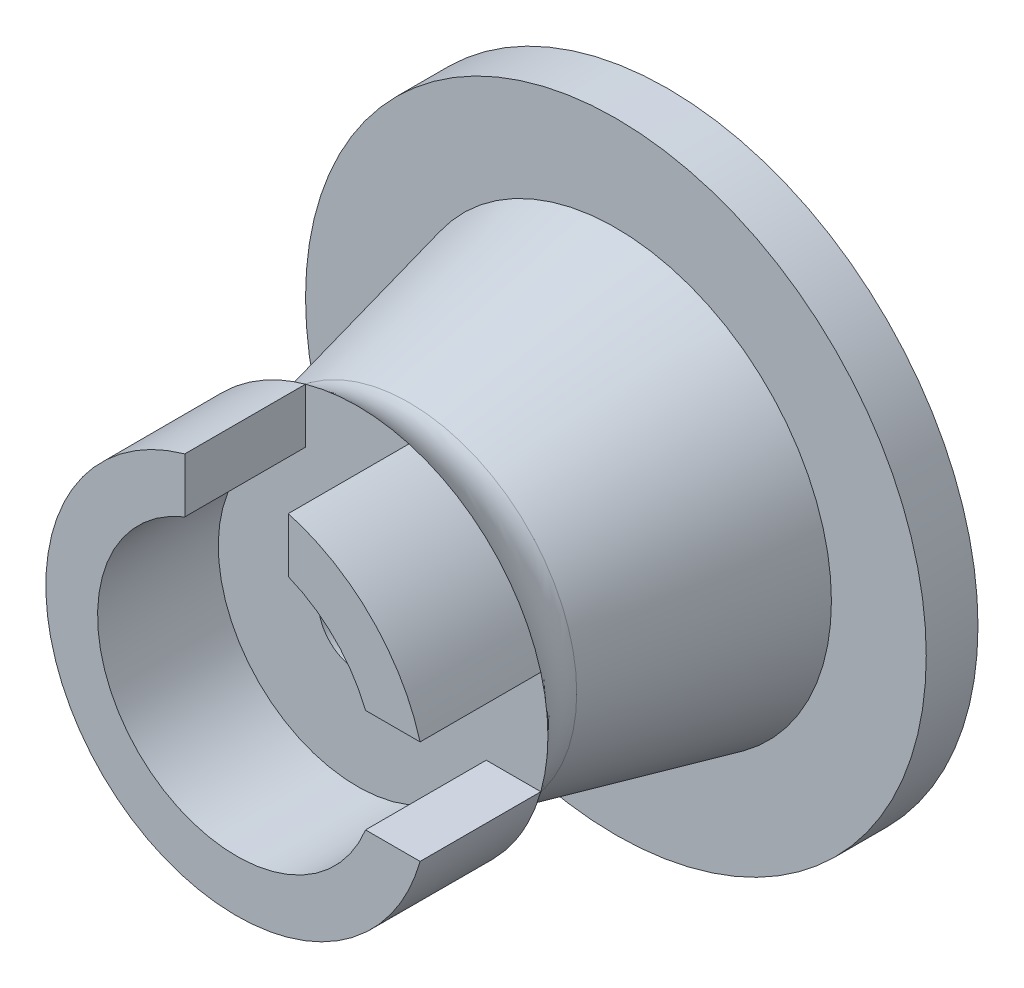
SolidWorks part; units mm, degrees
ref_plane "Front Plane" through (0, 0, 0) normal (0, 0, 1) x (1, 0, 0)
ref_plane "Top Plane" through (0, 0, 0) normal (0, 1, 0) x (1, 0, 0)
ref_plane "Right Plane" through (0, 0, 0) normal (1, 0, 0) x (0, 0, -1)
sketch "Sketch1" plane through (0, 0, 0) normal (0, 0, 1) x (1, 0, 0)
  circle A0 centre (0, 0) radius 18
  dimension "D1" = 36
extrude "Boss-Extrude1" add sketch "Sketch1" along normal blind 3
sketch "Sketch2" plane through (0, 0, 3) normal (0, 0, 1) x (1, 0, 0)
  circle A0 centre (0, 0) radius 12.5
  dimension "D1" = 25
extrude "Boss-Extrude2" add sketch "Sketch2" along normal blind 12 draft 13
sketch "Sketch3" [suppressed] plane through (0, 0, 15) normal (0, 0, 1) x (1, 0, 0)
  circle A0 centre (0, 0) radius 1.975
  dimension "D1" = 3.95
extrude "Cut-Extrude3" [suppressed] cut sketch "Sketch3" against normal through all contours A0
sketch "Sketch4" plane through (0, 0, 15) normal (0, 0, 1) x (1, 0, 0)
  circle A0 centre (0, 0) radius 2.25
  dimension "D1" = 4.5
sketch "Sketch6" plane through (0, 0, 15) normal (0, 0, 1) x (1, 0, 0)
  circle A0 centre (0, 0) radius 9.7296
  circle A1 centre (0, 0) radius 9.7296 construction
ref_plane "Plane1" through (0, 0, 18) normal (0, 0, 1) x (1, 0, 0)
sketch "Sketch7" plane through (0, 0, 18) normal (0, 0, 1) x (1, 0, 0)
  circle A0 centre (0, 0) radius 11.06
  dimension "D1" = 22.12
loft "Loft3" add profiles "Sketch7", "Sketch6" connector at (9.1786, -6.1706, 18) connector at (9.7296, 0, 15)
sketch "Sketch8" plane through (0, 0, 18) normal (0, 0, 1) x (1, 0, 0)
  line L1 (-10.6454, 3) -> (10.6454, 3)
  line L2 (-10.6454, 3) -> (-10.6454, -3)
  line L3 (-10.6454, -3) -> (10.6454, -3)
  line L4 (10.6454, 3) -> (10.6454, -3)
  line L5 (-10.6454, 3) -> (10.6454, -3) construction
  line L6 (-10.6454, -3) -> (10.6454, 3) construction
  line L7 (-3, 10.6454) -> (3, 10.6454)
  line L8 (-3, 10.6454) -> (-3, -10.6454)
  line L9 (-3, -10.6454) -> (3, -10.6454)
  line L10 (3, 10.6454) -> (3, -10.6454)
  line L11 (-3, 10.6454) -> (3, -10.6454) construction
  line L12 (-3, -10.6454) -> (3, 10.6454) construction
  circle A0 centre (0, 0) radius 8.06
  circle A1 centre (0, 0) radius 11.06
  dimension "D1" = 16.12
  dimension "D3" = 6
  dimension "D4" = 6
  dimension "D2" = 3
extrude "Boss-Extrude3" add sketch "Sketch8" along normal blind 7 contours A0 L8 L1 | A0 L1 L2 L3 | A0 L3 L8 | A0 L8 L9 L10 | A0 L10 L3 | A0 L1 L10 | L9 | L2 region at (-6.6036, 6.6036, 18) region at (-9.2523, 0, 18) region at (-10.8115, 0, 18) region at (-6.6036, -6.6036, 18) region at (0, -9.2523, 18) region at (0, -10.8115, 18) region at (6.6036, 6.6036, 18) region at (6.6036, -6.6036, 18)
sketch "Sketch10" plane through (0, 0, 18) normal (0, 0, 1) x (1, 0, 0)
  circle A0 centre (0, 0) radius 2.25
  dimension "D1" = 4.5
extrude "Cut-Extrude5" cut sketch "Sketch10" against normal through all
